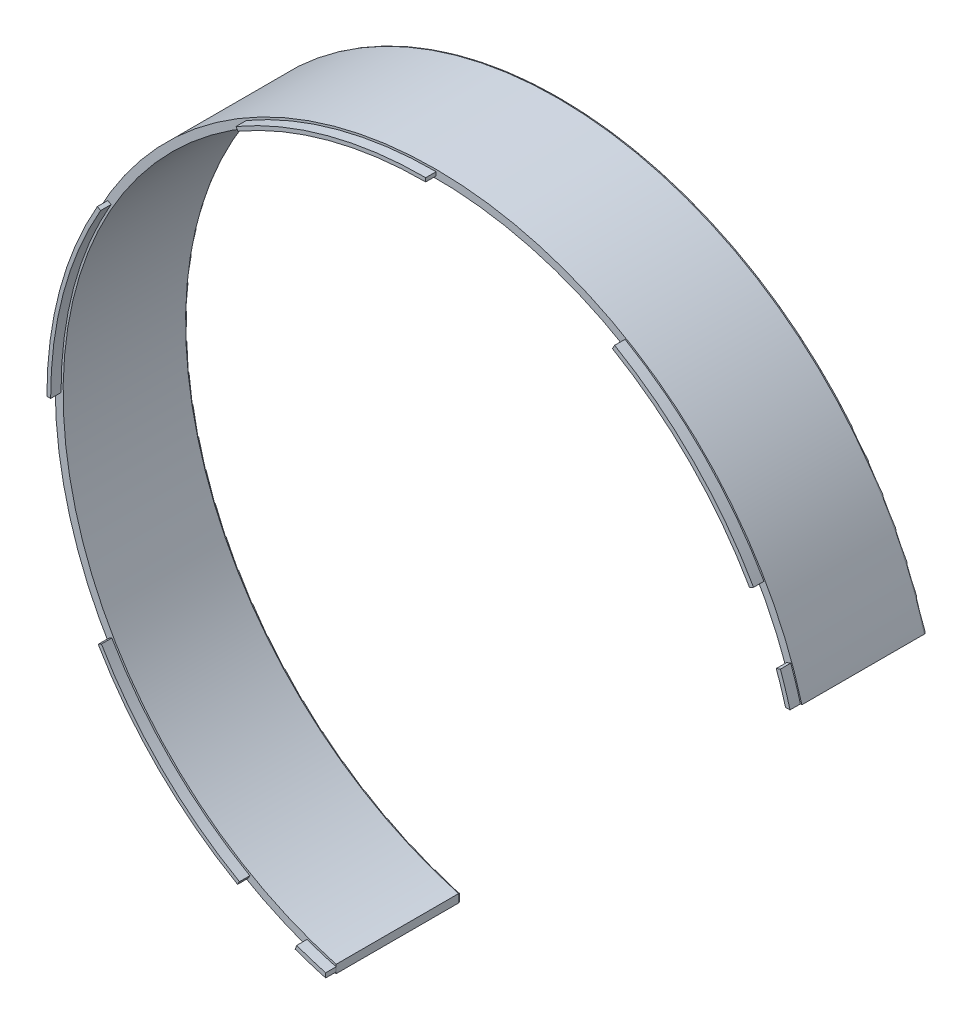
SolidWorks part; units mm, degrees
ref_plane "Front Plane" through (0, 0, 0) normal (0, 0, 1) x (1, 0, 0)
ref_plane "Top Plane" through (0, 0, 0) normal (0, 1, 0) x (1, 0, 0)
ref_plane "Right Plane" through (0, 0, 0) normal (1, 0, 0) x (0, 0, -1)
sketch "Sketch1" plane through (0, 0, 0) normal (0, 0, 1) x (1, 0, 0)
  line L4 (158.3829, 90.065) -> (156.4705, 88.9775) construction
  line L5 (91.4734, 157.5737) -> (90.3689, 155.671) construction
  line L6 (158.3829, 90.065) -> (156.4705, 88.9775)
  line L7 (91.4734, 157.5737) -> (90.3689, 155.671)
  line L24 (169.3197, 61.6675) -> (171.2921, 62.3883)
  line L25 (173.7721, 47.7) -> (175.9489, 47.7)
  line L26 (-90.8953, 157.6771) -> (-89.9946, 156.1186)
  line L27 (0.4815, 181.9994) -> (0.4748, 180.1994)
  line L28 (-181.9994, -0.4815) -> (-180.1994, -0.4748)
  line L29 (-157.6771, 90.8953) -> (-156.1186, 89.9946)
  line L30 (-90.1399, -158.1101) -> (-89.2502, -156.5454)
  line L31 (-157.3002, -91.5459) -> (-155.7435, -90.6422)
  line L32 (-47.7, -173.7721) -> (-47.7, -175.9489)
  line L33 (-61.6675, -169.3197) -> (-62.3883, -171.2921)
  arc A4 (156.4705, 88.9775) -> (90.3689, 155.671) centre (0, 0) ccw construction
  arc A5 (158.3829, 90.065) -> (91.4734, 157.5737) centre (0, 0) ccw construction
  arc A6 (156.4705, 88.9775) -> (90.3689, 155.671) centre (0, 0) ccw
  arc A7 (158.3829, 90.065) -> (91.4734, 157.5737) centre (0, 0) ccw
  arc A26 (173.7721, 47.7) -> (169.3197, 61.6675) centre (0, 0) ccw
  arc A27 (175.9489, 47.7) -> (171.2921, 62.3883) centre (0, 0) ccw
  arc A28 (0.4815, 181.9994) -> (-90.8953, 157.6771) centre (0, 0) ccw
  arc A29 (0.4748, 180.1994) -> (-89.9946, 156.1186) centre (0, 0) ccw
  arc A30 (-156.1186, 89.9946) -> (-180.1994, -0.4748) centre (0, 0) ccw
  arc A31 (-157.6771, 90.8953) -> (-181.9994, -0.4815) centre (0, 0) ccw
  arc A32 (-157.3002, -91.5459) -> (-90.1399, -158.1101) centre (0, 0) ccw
  arc A33 (-155.7435, -90.6422) -> (-89.2502, -156.5454) centre (0, 0) ccw
  arc A34 (-61.6675, -169.3197) -> (-47.7, -173.7721) centre (0, 0) ccw
  arc A35 (-62.3883, -171.2921) -> (-47.7, -175.9489) centre (0, 0) ccw
extrude "Boss-Extrude1" add sketch "Sketch1" against normal blind 5
sketch "Sketch2" plane through (0, 0, -5) normal (0, 0, -1) x (-1, 0, 0)
  line L0 (47.7, -172.7349) -> (47.7, -176.674)
  line L2 (-176.674, 47.7) -> (-172.7349, 47.7)
  line L4 (-173.7721, 47.7) -> (-175.9489, 47.7) construction
  line L5 (47.7, -175.9489) -> (47.7, -173.7721) construction
  arc A0 (47.7, -172.7349) -> (-172.7349, 47.7) centre (0, 0) ccw
  arc A2 (47.7, -176.674) -> (-176.674, 47.7) centre (0, 0) ccw
  arc A4 (180.1994, -0.4748) -> (156.1186, 89.9946) centre (0, 0) ccw construction
  arc A5 (181.9994, -0.4815) -> (157.6771, 90.8953) centre (0, 0) ccw construction
  dimension "D1" = 1
  dimension "D2" = 1
extrude "Boss-Extrude2" add sketch "Sketch2" along normal blind 60
fillet "Fillet1" radius 1 3 edges at (-129.4005, 129.4005, -65) (174.7045, 47.7, -65) (-126.7135, 126.7135, -65)
fillet "Fillet2" radius 1 1 edges at (-47.7, -174.7051, -65)
